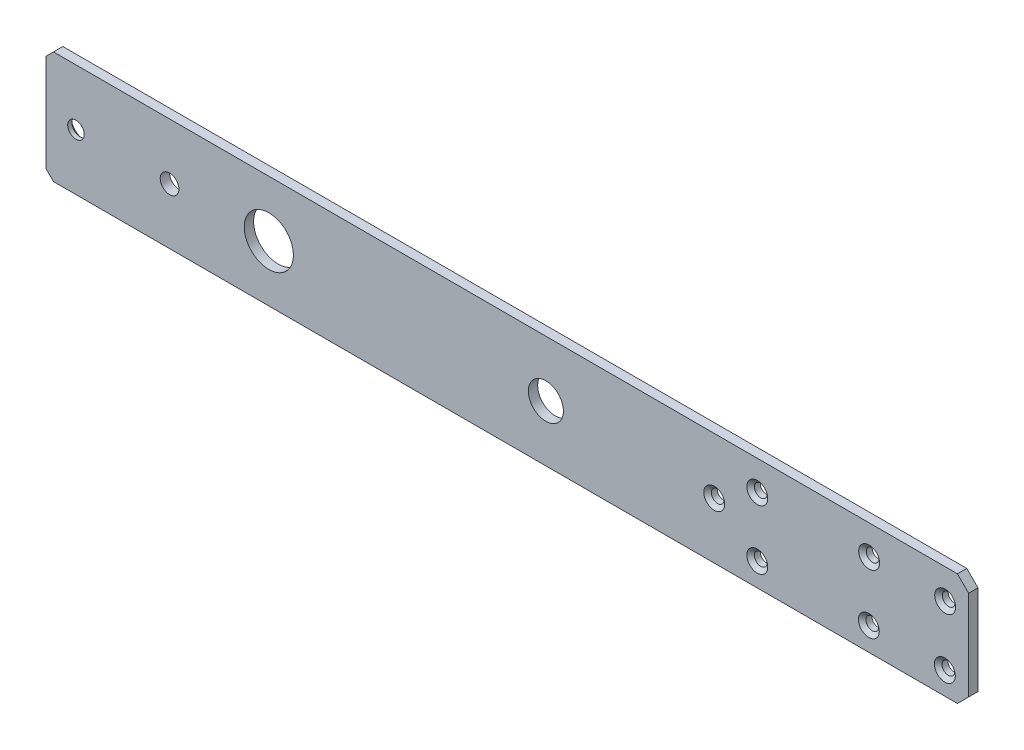
SolidWorks part; units mm, degrees
material "6061-T6 (SS)"
ref_plane "Front Plane" through (0, 0, 0) normal (0, 0, 1) x (1, 0, 0)
ref_plane "Top Plane" through (0, 0, 0) normal (0, 1, 0) x (1, 0, 0)
ref_plane "Right Plane" through (0, 0, 0) normal (1, 0, 0) x (0, 0, -1)
sketch "Sketch1" plane through (0, 0, 0) normal (0, 0, 1) x (1, 0, 0)
  line L0 (0, 19.05) -> (-28.575, 19.05)
  line L1 (0, -19.05) -> (247.2819, -19.05)
  line L2 (0, -19.05) -> (0, 19.05) construction
  line L3 (0, 19.05) -> (254, 19.05)
  line L5 (-28.575, 19.05) -> (-28.575, -19.05)
  line L6 (-28.575, -19.05) -> (0, -19.05)
  line L8 (254, 19.05) -> (247.2819, -19.05)
  circle A1 centre (0, 0) radius 8.3344
  dimension "D3" = 16.6687
  dimension "D1" = 38.1
  dimension "D2" = 254
  dimension "D4" = 80
extrude "Boss-Extrude1" add sketch "Sketch1" along normal mid plane 3.175
hole_wizard "#6 Clearance Hole3" positions "Sketch8" profile "Sketch7" hole size "#6" standard "ANSI Inch" end condition through all
sketch "Sketch8" plane through (0, 0, 1.5875) normal (0, 0, 1) x (1, 0, 0)
  point P0 (229.3887, 8.9238)
  point P3 (229.2824, -11.3468)
  point P6 (203.5032, -11.1439)
  point P9 (203.6088, 8.9914)
  point P12 (165.6722, 8.9914)
  point P15 (165.6722, -11.1439)
  point P18 (151.0672, 0)
sketch "Sketch7" plane through (229.3887, 8.9238, 1.5875) normal (1, 0, 0) x (0, -1, 0)
  line L0 (0, 0) -> (0, 3.175)
  line L1 (0, 3.175) -> (2.1526, 3.175)
  line L2 (2.1526, 3.175) -> (2.1526, 0)
  line L5 (2.1526, 0) -> (0, 0)
  line L11 (0, -6.35) -> (0, 107.95) construction
  dimension "Thru Hole Dia." = 4.3053
  dimension "Thru Hole Depth" = 3.175
sketch "Sketch9" plane through (0, 0, 1.5875) normal (0, 0, 1) x (1, 0, 0)
  line L0 (254, 19.05) -> (247.2819, -19.05)
  line L1 (254, 19.05) -> (237.3521, 19.05)
  line L2 (254, 19.05) -> (-28.575, 19.05) construction
  line L3 (237.3521, 19.05) -> (237.3521, -19.05)
  line L4 (-28.575, -19.05) -> (247.2819, -19.05) construction
  line L5 (237.3521, -19.05) -> (247.2819, -19.05)
  line L6 (243.8073, 17.5595) -> (237.0893, -20.5405) construction
extrude "Cut-Extrude1" cut sketch "Sketch9" against normal through all
chamfer "Chamfer1" distance 3.81 angle 45 4 edges at (-28.575, -19.05, 0) (-28.575, 19.05, 0) (237.3521, 19.05, 0) (237.3521, -19.05, 0)
hole_wizard "CSK for #6 Flat Head Machine Screw (100)2" positions "Sketch12" profile "Sketch13" countersink size "#6" standard "ANSI Inch" end condition through all
sketch "Sketch12" plane through (0, 0, 1.5875) normal (0, 0, 1) x (1, 0, 0)
  point P0 (203.6088, 8.9914)
  point P3 (203.5032, -11.1439)
  point P6 (229.2824, -11.3468)
  point P9 (229.3887, 8.9238)
  point P12 (165.6722, 8.9914)
  point P15 (165.6722, -11.1439)
  point P18 (151.0672, 0)
sketch "Sketch13" plane through (203.6088, 8.9914, 1.5875) normal (1, 0, 0) x (0, -1, 0)
  line L0 (0, 0) -> (0, 3.175)
  line L1 (0, 3.175) -> (2.1526, 3.175)
  line L2 (2.1526, 3.175) -> (2.1526, 1.1669)
  line L3 (2.1526, 1.1669) -> (3.5433, 0)
  line L5 (3.5433, 0) -> (0, 0)
  line L6 (-2.1526, 1.1669) -> (-3.5433, 0) construction
  line L11 (0, -6.35) -> (0, 107.95) construction
  dimension "Thru Hole Dia." = 4.3053
  dimension "Thru Hole Depth" = 3.175
  dimension "Near C'Sink Dia." = 7.0866
  dimension "Near C'Sink Angle" = 100
sketch "Sketch14" plane through (0, 0, 1.5875) normal (0, 0, 1) x (1, 0, 0)
  line L1 (-24.765, 19.05) -> (-75.565, 19.05)
  line L2 (-24.765, 19.05) -> (-24.765, -19.05)
  line L3 (-24.765, -19.05) -> (-75.565, -19.05)
  line L4 (-75.565, 19.05) -> (-75.565, -19.05)
  dimension "D1" = 50.8
extrude "Boss-Extrude2" add sketch "Sketch14" against normal through all
chamfer "Chamfer2" distance 2.54 angle 45 2 edges at (-75.565, 19.05, 0) (-75.565, -19.05, 0)
hole_wizard "CSK for #10 Flat Head Machine Screw (100)1" positions "Sketch15" profile "Sketch16" countersink size "#10" standard "ANSI Inch" end condition through all
sketch "Sketch15" plane through (0, 0, -1.5875) normal (0, 0, 1) x (1, 0, 0)
  line L0 (0, 0) -> (-75.565, 0) construction
  line L1 (-75.565, 16.51) -> (-75.565, -16.51) construction
  point P0 (-65.405, 0)
  dimension "D1" = 10.16
sketch "Sketch16" plane through (-65.405, 0, -1.5875) normal (1, 0, 0) x (0, 1, 0)
  line L0 (0, 0) -> (0, 3.175)
  line L1 (0, 3.175) -> (2.8067, 3.175)
  line L2 (2.8067, 3.175) -> (2.8067, 1.7477)
  line L3 (2.8067, 1.7477) -> (4.8895, 0)
  line L5 (4.8895, 0) -> (0, 0)
  line L6 (-2.8067, 1.7477) -> (-4.8895, 0) construction
  line L11 (0, -6.35) -> (0, 107.95) construction
  dimension "Thru Hole Dia." = 5.6134
  dimension "Thru Hole Depth" = 3.175
  dimension "Near C'Sink Dia." = 9.779
  dimension "Near C'Sink Angle" = 100
hole_wizard "1/4 (0.25) Diameter Hole1" positions "Sketch19" profile "Sketch20" hole size "1/4" standard "ANSI Inch" end condition through all
sketch "Sketch19" plane through (0, 0, -1.5875) normal (0, 0, -1) x (-1, 0, 0)
  line L0 (75.565, 0) -> (33.655, 0) construction
  line L1 (75.565, 16.51) -> (75.565, -16.51) construction
  circle A1 centre (65.405, 0) radius 4.8895 construction
  point P0 (33.655, 0)
  dimension "D1" = 31.75
sketch "Sketch20" plane through (-33.655, 0, -1.5875) normal (1, 0, 0) x (0, 1, 0)
  line L0 (0, 0) -> (0, 3.175)
  line L1 (0, 3.175) -> (3.175, 3.175)
  line L2 (3.175, 3.175) -> (3.175, 0)
  line L5 (3.175, 0) -> (0, 0)
  line L11 (0, -6.35) -> (0, 107.95) construction
  dimension "Thru Hole Dia." = 6.35
  dimension "Thru Hole Depth" = 3.175
hole_wizard "15/32 (0.46875) Diameter Hole1" positions "Sketch21" profile "Sketch22" hole size "15/32" standard "ANSI Inch" end condition through all
sketch "Sketch21" plane through (0, 0, -1.5875) normal (0, 0, -1) x (-1, 0, 0)
  line L0 (75.565, 16.51) -> (75.565, -16.51) construction
  point P0 (-93.9672, 0)
  dimension "D1" = 169.5322
sketch "Sketch22" plane through (93.9672, 0, -1.5875) normal (1, 0, 0) x (0, 1, 0)
  line L0 (0, 0) -> (0, 3.175)
  line L1 (0, 3.175) -> (5.9531, 3.175)
  line L2 (5.9531, 3.175) -> (5.9531, 0)
  line L5 (5.9531, 0) -> (0, 0)
  line L11 (0, -6.35) -> (0, 107.95) construction
  dimension "Thru Hole Dia." = 11.9062
  dimension "Thru Hole Depth" = 3.175
